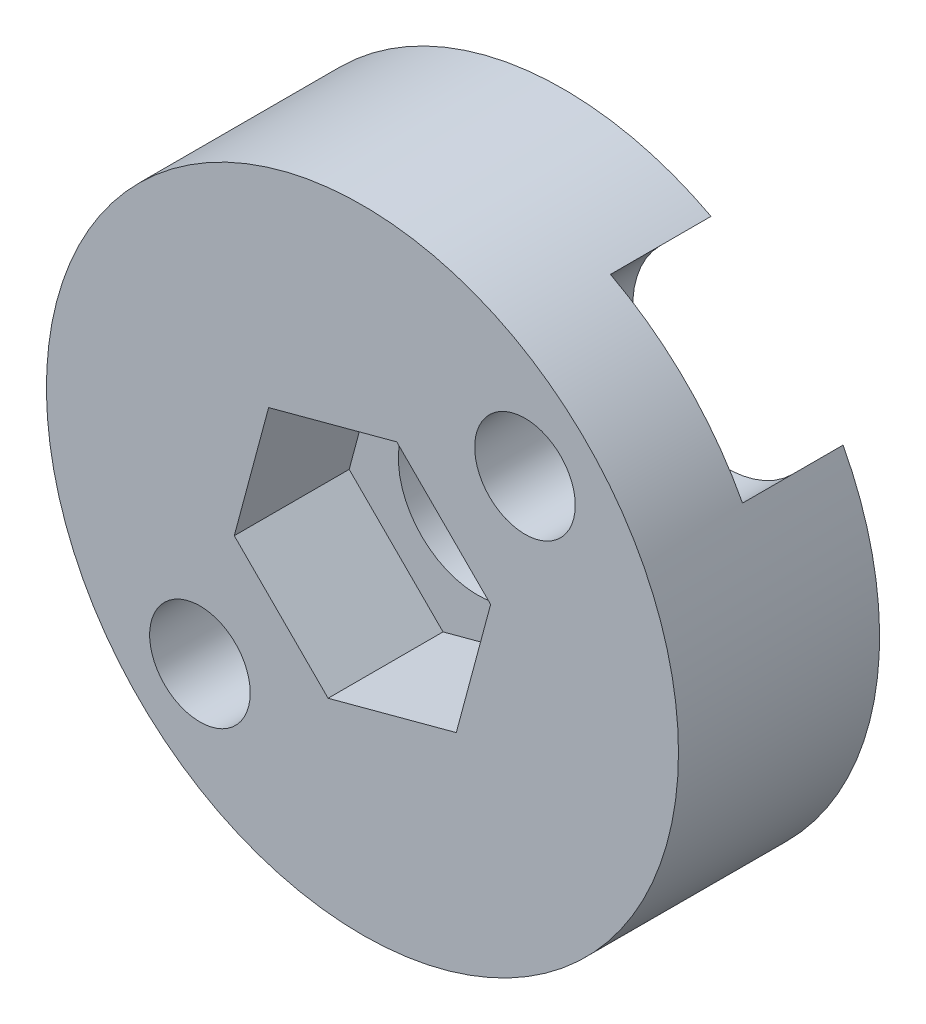
SolidWorks part; units mm, degrees
ref_plane "Plano frontal" through (0, 0, 0) normal (0, 0, 1) x (1, 0, 0)
ref_plane "Plano superior" through (0, 0, 0) normal (0, 1, 0) x (1, 0, 0)
ref_plane "Plano direito" through (0, 0, 0) normal (1, 0, 0) x (0, 0, -1)
sketch "Esboço1" plane through (0, 0, 0) normal (0, 0, 1) x (1, 0, 0)
  line L1 (5.6569, 5.6569) -> (-5.6569, 5.6569) construction
  line L2 (5.6569, 5.6569) -> (5.6569, -5.6569) construction
  line L3 (5.6569, -5.6569) -> (-5.6569, -5.6569) construction
  line L4 (-5.6569, 5.6569) -> (-5.6569, -5.6569) construction
  line L5 (5.6569, 5.6569) -> (-5.6569, -5.6569) construction
  line L6 (5.6569, -5.6569) -> (-5.6569, 5.6569) construction
  circle A0 centre (0, 0) radius 11
  circle A1 centre (5.6569, 5.6569) radius 1.75
  circle A2 centre (-5.6569, 5.6569) radius 1.75 construction
  circle A3 centre (-5.6569, -5.6569) radius 1.75
  circle A4 centre (5.6569, -5.6569) radius 1.75 construction
  circle A5 centre (0, 0) radius 2.75
  dimension "D1" = 22
  dimension "D3" = 3.5
  dimension "D4" = 5.5
  dimension "D2" = 16
extrude "Ressalto-extrusão1" add sketch "Esboço1" along normal blind 7
sketch "Esboço10" plane through (0, 0, 7) normal (0, 0, 1) x (1, 0, 0)
  line L0 (-5.6569, -5.6569) -> (5.6569, 5.6569) construction
  line L1 (-1.1954, -4.4614) -> (3.266, -3.266)
  line L2 (3.266, -3.266) -> (4.4614, 1.1954)
  line L3 (4.4614, 1.1954) -> (1.1954, 4.4614)
  line L4 (1.1954, 4.4614) -> (-3.266, 3.266)
  line L5 (-3.266, 3.266) -> (-4.4614, -1.1954)
  line L6 (-4.4614, -1.1954) -> (-1.1954, -4.4614)
  line L7 (0, 0) -> (-5.369, 5.369) construction
  circle A0 centre (0, 0) radius 4 construction
  dimension "D1" = 8
extrude "Corte-extrusão5" cut sketch "Esboço10" against normal blind 4
sketch "Esboço12" plane through (0, 0, 0) normal (0, 0, -1) x (-1, 0, 0)
  line L1 (-3.3588, 7.955) -> (-5.1328, 9.729)
  line L4 (-7.955, 3.3588) -> (-9.729, 5.1328)
  circle A12 centre (0, 0) radius 11 construction
  arc A13 (-7.955, 3.3588) -> (-3.3588, 7.955) centre (-5.6569, 5.6569) ccw
  circle A14 centre (0, 0) radius 11
  arc A15 (-5.1328, 9.729) -> (6.675, 8.7433) centre (0, 0) ccw
  point P21 (-2.4069, 5.6569)
  circle M11 centre (0, 0) radius 11
  circle M12 centre (-5.6569, 5.6569) radius 1.75
  dimension "D2" = 0
extrude "Corte-extrusão6" cut sketch "Esboço12" against normal offset from surface (3.5 mm away) 3.5 contours L4 A13 L1 M11 M12 region at (3.432, 3.432, 0) up to face at (0, 0, 7)
ref_axis "Eixo1" through (0, 0, 3) along (0, 0, -1)
pattern_circular "PadrãoCircular1" count 2 over 360 about axis through (0, 0, 3) along (0, 0, -1) of "Corte-extrusão6"
